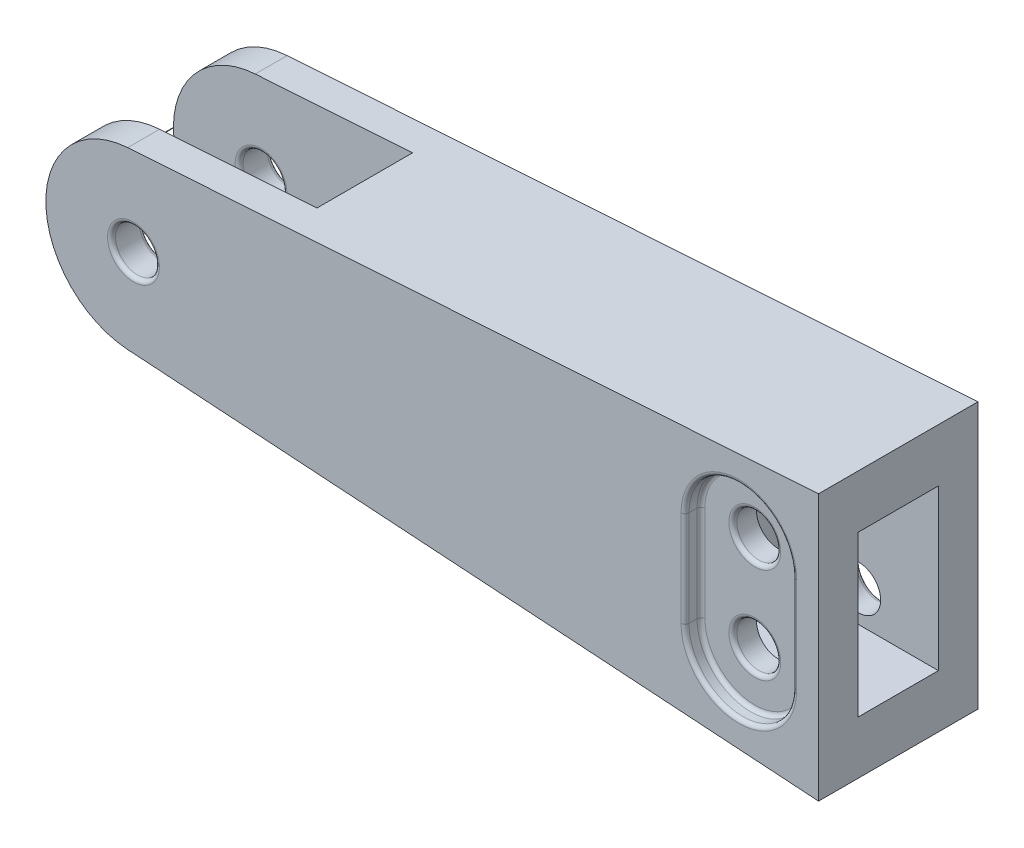
SolidWorks part; units mm, degrees
ref_plane "Front Plane" through (0, 0, 0) normal (0, 0, 1) x (1, 0, 0)
ref_plane "Top Plane" through (0, 0, 0) normal (0, 1, 0) x (1, 0, 0)
ref_plane "Right Plane" through (0, 0, 0) normal (1, 0, 0) x (0, 0, -1)
sketch "Sketch1" plane through (0, 0, 0) normal (0, 0, 1) x (1, 0, 0)
  line L1 (43.0973, 0) -> (50043.0973, 0) construction
  line L2 (0, 21.9801) -> (0, 50021.9801) construction
  line L5 (-147.5823, 10.9687) -> (-60.9237, 16.6957)
  line L6 (-60.9237, -16.6957) -> (-17.5179, -19.5642) construction
  line L7 (-60.9237, 16.6957) -> (-60.9237, -16.6957) construction
  line L8 (-60.9237, 16.6957) -> (-60.9237, -16.6957)
  line L9 (-147.5823, -10.9687) -> (-60.9237, -16.6957)
  arc A1 (-147.5823, 10.9687) -> (-147.5823, -10.9687) centre (-146.8574, 0) ccw
  point P9 (0, 0)
  dimension "D1" = 146.8574
extrude "Boss-Extrude1" add sketch "Sketch1" along normal up to surface (20 mm away) contours A1 region at (-104.6886, 0, 0)
sketch "Sketch2" plane through (-60.9237, 0, 0) normal (1, 0, 0) x (0, 0, -1)
  line L0 (-10, -20) -> (-10, 20) construction
  line L4 (-15.035, -10.035) -> (-4.965, -10.035)
  line L5 (-15.035, -10.035) -> (-15.035, 10.035)
  line L6 (-15.035, 10.035) -> (-4.965, 10.035)
  line L16 (-20, -20) -> (0, -20) construction
  line L17 (-20, 20) -> (-20, -20) construction
  line L18 (0, 20) -> (-20, 20) construction
  line L19 (0, -20) -> (0, 20) construction
  line L20 (-4.965, -10.035) -> (-4.965, 10.035)
  line L21 (-15.035, -10.035) -> (-4.965, 10.035) construction
  line L22 (-15.035, 10.035) -> (-4.965, -10.035) construction
  line L23 (0, 0) -> (-20, 0) construction
  point P2 (-10, 0)
  point P6 (0, 16.6493)
  point P15 (-10, 0)
  point P16 (0, 0)
  point P17 (0, 0)
  point P18 (0, 0)
  point P19 (0, 0)
  dimension "D2" = 10.07
  dimension "D3" = 20.07
  dimension "D1" = 40
  dimension "D4" = 20
  dimension "D5" = 10
extrude "Cut-Extrude1" cut sketch "Sketch2" against normal blind 20
sketch "Sketch4" plane through (0, 0, 0) normal (0, 1, 0) x (1, 0, 0)
  line L0 (-60.9237, -20) -> (-147.5823, -20) construction
  line L5 (-157.85, 0) -> (-157.85, -20) construction
  line L6 (-157.85, -4) -> (-127.85, -4)
  line L7 (-157.85, -4) -> (-157.85, -16)
  line L10 (-157.85, -16) -> (-127.85, -16)
  line L15 (-127.85, -4) -> (-127.85, -16)
  line L16 (-157.85, -4) -> (-127.85, -16) construction
  line L17 (-157.85, -16) -> (-127.85, -4) construction
  line L18 (-147.5823, 0) -> (-157.85, 0) construction
  point P4 (-142.85, -10)
  dimension "D1" = 4
  dimension "D2" = 4
  dimension "D3" = 30
extrude "Cut-Extrude2" cut sketch "Sketch4" against normal through all both and the other way through all
sketch "Sketch5" plane through (0, 0, 0) normal (0, 0, -1) x (-1, 0, 0)
  circle A0 centre (146.8574, 0) radius 2.75
  dimension "D1" = 5.5
extrude "Cut-Extrude3" cut sketch "Sketch5" against normal through all
sketch "Sketch6" plane through (0, 0, 0) normal (0, 0, -1) x (-1, 0, 0)
  line L1 (0, 0) -> (50000, 0) construction
  line L2 (60.9237, 16.6957) -> (60.9237, -16.6957) construction
  circle A0 centre (70.9237, -6) radius 2.75
  circle A1 centre (70.9237, 6) radius 2.75
  dimension "D1" = 5.5
  dimension "D2" = 10
  dimension "D3" = 6
extrude "Cut-Extrude4" cut sketch "Sketch6" against normal through all
sketch "Sketch8" plane through (0, 0, 0) normal (0, 0, -1) x (-1, 0, 0)
  line L0 (64.1737, 6) -> (64.1737, -6)
  line L2 (77.6737, 6) -> (77.6737, -6)
  circle A0 centre (70.9237, -6) radius 2.75 construction
  circle A1 centre (70.9237, 6) radius 2.75 construction
  circle A2 centre (70.9237, -6) radius 2.75 construction
  circle A3 centre (70.9237, 6) radius 2.75 construction
  arc A4 (64.1737, -6) -> (77.6737, -6) centre (70.9237, -6) ccw
  arc A5 (77.6737, 6) -> (64.1737, 6) centre (70.9237, 6) ccw
  circle A6 centre (70.9237, 6) radius 6.75 construction
  circle A7 centre (70.9237, -6) radius 6.75 construction
  dimension "D1" = 4
extrude "Cut-Extrude5" cut sketch "Sketch8" against normal blind 2
ref_plane "Plane1" through (0, 0, 10) normal (0, 0, -1) x (-1, 0, 0)
mirror "Mirror1" about plane through (0, 0, 10) normal (0, 0, -1) of "Cut-Extrude5"
fillet "Fillet2" radius 0.5 24 edges at (-70.9237, -12.75, 2) (-64.1737, 0, 2) (-70.9237, 12.75, 2) (-70.9237, -12.75, 0) (-64.1737, 0, 0) (-70.9237, 12.75, 0) (-70.9237, -12.75, 18) (-64.1737, 0, 18) (-70.9237, 12.75, 18) (-70.9237, -12.75, 20) (-64.1737, 0, 20) (-70.9237, 12.75, 20) (-149.6074, 0, 4) (-149.6074, 0, 0) (-144.1074, 0, 16) (-149.6074, 0, 20) (-68.1737, -6, 18) (-68.1737, 6, 18) (-73.6737, -6, 2) (-73.6737, 6, 2) (-77.6737, 0, 18) (-77.6737, 0, 20) (-77.6737, 0, 2) (-77.6737, 0, 0)
